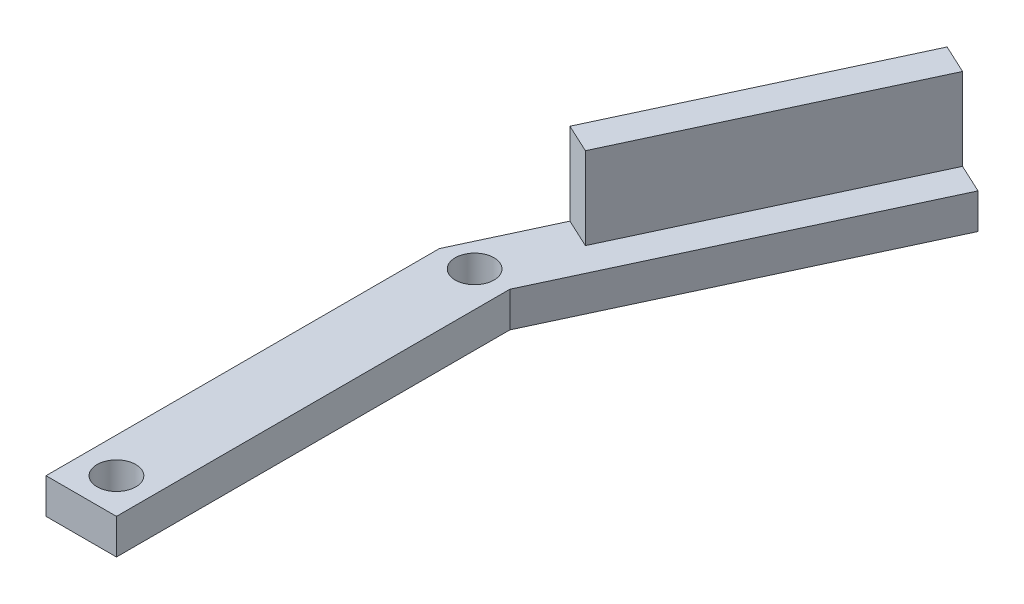
SolidWorks part; units mm, degrees
ref_plane "Front Plane" through (0, 0, 0) normal (0, 0, 1) x (1, 0, 0)
ref_plane "Top Plane" through (0, 0, 0) normal (0, 1, 0) x (1, 0, 0)
ref_plane "Right Plane" through (0, 0, 0) normal (1, 0, 0) x (0, 0, -1)
sketch "Sketch1" plane through (0, 0, 0) normal (0, 1, 0) x (1, 0, 0)
  line L0 (-3, 3) -> (-3, 30.5)
  line L5 (-3, 3) -> (3, 3)
  line L6 (-3, 3) -> (-3, -3)
  line L8 (-3, -3) -> (3, -3)
  line L12 (3, 3) -> (3, -3)
  line L13 (-3, 3) -> (3, -3) construction
  line L14 (-3, -3) -> (3, 3) construction
  line L19 (-3, 30.5) -> (3, 30.5)
  line L20 (3, 30.5) -> (3, 3)
  line L21 (3, 30.5) -> (15.6785, 57.6892)
  line L22 (15.6785, 57.6892) -> (10.7502, 59.9874)
  line L25 (10.7502, 59.9874) -> (-3, 30.5)
  line L26 (13.2144, 58.8383) -> (0.6973, 31.9954)
  line L27 (3, 36.9335) -> (0.5358, 38.0826)
  circle A4 centre (0, 0) radius 1.65
  circle A5 centre (0, 30.5) radius 1.65
  dimension "D1" = 3.3
  dimension "D6" = 30
  dimension "D7" = 3.3
  dimension "D2" = 6
  dimension "D3" = 6
  dimension "D4" = 27.5
  dimension "D5" = 205
extrude "Boss-Extrude1" add sketch "Sketch1" along normal blind 3 contours A5 L19 L21 L22 L25 | A5 L19 L0 L5 L20 | L12 L5 L6 L8 A4 | A5 L25 L19 region at (0, 0, -16.4028) region at (0, 0, -2.9151) region at (0.1852, 0, -34.42) region at (8.0976, 0, -44.6356)
extrude "Boss-Extrude2" add sketch "Sketch1<4>" along normal blind 10 contours L22 L25 region at (6.8751, 0, -48.4604)
sketch "Sketch1<4>" plane through (0, 0, 0) normal (0, 1, 0) x (1, 0, 0) same geometry as "Sketch1"
